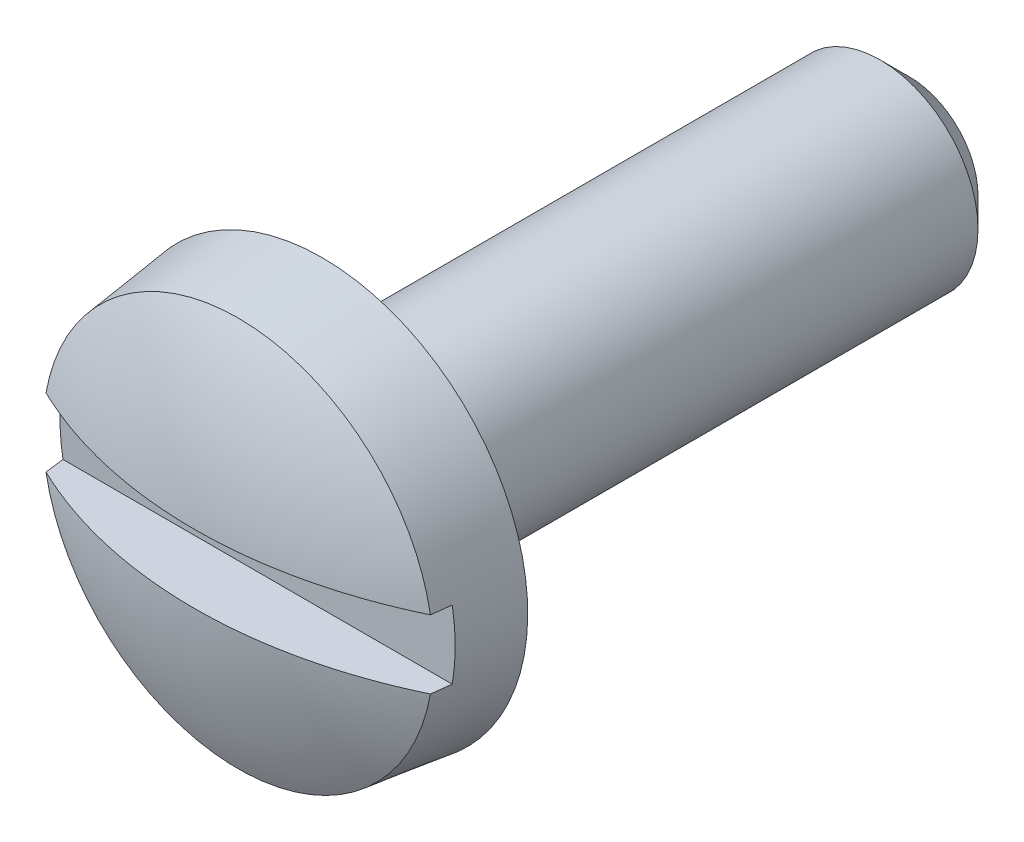
SolidWorks part; units mm, degrees
material "AISI 304"
ref_plane "Front" through (0, 0, 0) normal (0, 0, 1) x (1, 0, 0)
ref_plane "Top" through (0, 0, 0) normal (0, 1, 0) x (1, 0, 0)
ref_plane "Right" through (0, 0, 0) normal (1, 0, 0) x (0, 0, -1)
sketch "Sketch1" plane through (0, 0, 0) normal (0, 0, 1) x (1, 0, 0)
  circle A0 centre (0, 0) radius 6.6675
  dimension "Head Dia" = 13.335
extrude "Extrude3" add sketch "Sketch1" along normal blind 4.191
sketch "Sketch11" plane through (0, 0, 0) normal (1, 0, 0) x (0, 0, -1)
  line L0 (0, 0) -> (-4.445, 0) construction
  line L3 (0, 6.6675) -> (-4.191, 6.6675) construction
  line L4 (-4.191, 6.6675) -> (-4.191, -6.6675) construction
  line L5 (-4.445, 6.9342) -> (0, 6.9342)
  line L7 (0, 6.9342) -> (0, 6.6675)
  line L8 (-2.7242, 6.333) -> (0, 6.6675)
  line L9 (0, -6.6675) -> (0, 6.6675) construction
  line L13 (-4.191, 0) -> (-4.445, 0)
  line L14 (-4.445, 0) -> (-4.445, 6.9342)
  arc A0 (-2.7242, 6.333) -> (-4.191, 0) centre (10.2136, 0) ccw
  dimension "D3" = 0.254
  dimension "D5" = 0.2667
  dimension "D1" = 7
  dimension "D2" = 1.4668
revolve "Cut-Revolve3" cut sketch "Sketch11" angle 360 about L0
sketch "Sketch4" plane through (0, 0, 0) normal (1, 0, 0) x (0, 0, -1)
  line L0 (0, 0) -> (19.05, 0)
  line L3 (19.05, 0) -> (19.05, 3.175)
  line L4 (19.05, 3.175) -> (0, 3.175)
  line L6 (0, 3.175) -> (0, 0)
  line L9 (19.05, 3.175) -> (19.05, -3.175) construction
  dimension "length" = 19.05
  dimension "dia" = 6.35
revolve "Revolve1" add sketch "Sketch4" angle 360 about L0
sketch "Sketch13" plane through (0, 0, -19.05) normal (0, 0, -1) x (-1, 0, 0)
  circle A2 centre (0, 0) radius 3.175
curve "Helix/Spiral1" pitch 1.27 height 19.05 turns 15
chamfer "Chamfer2" distance 0.9525 angle 45 1 edges at (3.175, 0, -19.05)
sketch "Sketch14" plane through (0, 0, 0) normal (1, 0, 0) x (0, 0, -1)
  line L0 (19.05, 3.2147) -> (20.1612, 3.2147)
  line L1 (20.1612, 3.2147) -> (19.685, 2.3555)
  line L2 (19.685, 2.3555) -> (19.5262, 2.3555)
  line L3 (19.5262, 2.3555) -> (19.05, 3.2147)
  line L4 (19.2881, 2.7851) -> (19.9231, 2.7851) construction
  dimension "D1" = 0.1588
  dimension "D2" = 58
  dimension "D3" = 0.635
  dimension "D4" = 0.0397
sweep "Cut-Sweep1" [suppressed] cut profiles "Sketch14" path "Helix/Spiral1"
ref_plane "Plane1" through (0, 0, 19.05) normal (0, 0, -1) x (-1, 0, 0)
sketch "Sketch29" [suppressed] plane through (0, 0, 19.05) normal (0, 0, -1) x (-1, 0, 0)
  circle A0 centre (0, 0) radius 3.175 construction
  circle A1 centre (0, 0) radius 3.175
  point P3 (0, -3.175)
  point P4 (0, 3.175)
extrude "Extrude11" [suppressed] add sketch "Sketch29" against normal up to surface (19.05 mm away)
ref_plane "Plane2" through (0, 0, 4.191) normal (0, 0, 1) x (1, 0, 0)
sketch "Sketch26" plane through (0, 0, 0) normal (0, 0, 1) x (1, 0, 0)
  circle A1 centre (0, 0) radius 0.5461
  dimension "D1" = 1.0922
extrude "Extrude13" [suppressed] add sketch "Sketch26" along normal up to surface (4.1806 mm away)
sketch "Sketch31" plane through (0, 0, 4.191) normal (0, 0, 1) x (1, 0, 0)
  line L0 (-6.6675, 1.1112) -> (6.6675, -1.1112) construction
  line L1 (-6.6675, 1.1112) -> (6.6675, 1.1113)
  line L2 (-6.6675, 1.1112) -> (-6.6675, -1.1113)
  line L3 (-6.6675, -1.1113) -> (6.6675, -1.1112)
  line L4 (6.6675, 1.1113) -> (6.6675, -1.1112)
  circle A0 centre (0, 0) radius 6.6675 construction
  dimension "D1" = 2.2225
extrude "Extrude15" cut sketch "Sketch31" against normal blind 2.0955
sketch "Sketch18" plane through (0, 0, 0) normal (1, 0, 0) x (0, 0, -1)
  line L1 (19.05, 3.175) -> (0, 3.175) construction
  point P0 (17.145, -3.175)
  point P1 (17.78, 3.175)
  point P2 (-4.191, 1.1113)
  dimension "D1" = 1.27
  dimension "D2" = 1.905
other "DeleteFace1" [suppressed]
equation "\"D3@Helix/Spiral1\" = \"length@Sketch4\""
equation "\"D1@Sketch14\" = \"D4@Helix/Spiral1\" * .125"
equation "\"D3@Sketch14\" = \"D4@Helix/Spiral1\" * .5"
equation "\"D5@Sketch11\" = \"Head Dia@Sketch1\" * .02"
equation "\"D4@Sketch14\" = \"D1@Sketch14\" * .25"
equation "\"D1@Chamfer2\" = \"D4@Helix/Spiral1\" * .75"
equation "\"D1@Sketch18\" = \"D4@Helix/Spiral1\""
equation "\"D2@Sketch18\" = \"D4@Helix/Spiral1\" * 1.5"
equation "\"D1@Extrude15\" = \"Head Ht@Extrude3\" * .5"
equation "\"D2@Sketch11\" = \"Head Ht@Extrude3\" * .35"
equation "\"D1@Sketch31\" = \"D4@Helix/Spiral1\" * 1.75"
